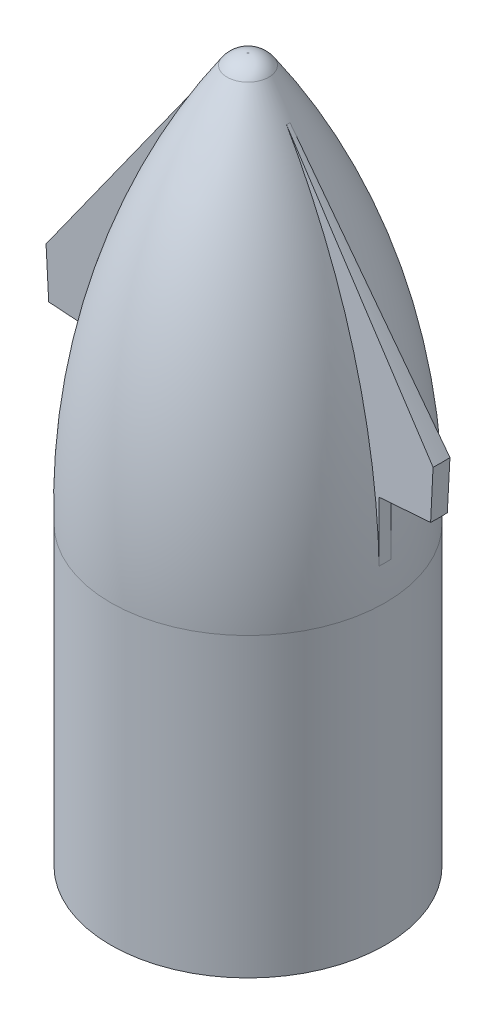
SolidWorks part; units mm, degrees
material "PET"
ref_plane "Front Plane" through (0, 0, 0) normal (0, 0, 1) x (1, 0, 0)
ref_plane "Top Plane" through (0, 0, 0) normal (0, 1, 0) x (1, 0, 0)
ref_plane "Right Plane" through (0, 0, 0) normal (1, 0, 0) x (0, 0, -1)
sketch "Sketch1" plane through (0, 0, 0) normal (0, 0, 1) x (1, 0, 0)
  line L0 (0, 0) -> (50.9, 0)
  line L1 (50.9, 0) -> (50.9, 110)
  line L2 (0, 3) -> (47.9, 3)
  line L3 (0, 261.1926) -> (0.2914, 261.1926)
  line L4 (47.9, 3) -> (47.9, 110.0403)
  line L5 (0, 258.1926) -> (0.2914, 258.1926)
  line L6 (0, 261.1926) -> (0, 258.1926)
  line L7 (0, 3) -> (0, 0)
  arc A0 (7.7342, 257.2527) -> (50.9, 110) centre (-199.0104, 116.6942) cw
  arc A1 (0.2914, 261.1926) -> (7.7342, 257.2527) centre (0.2914, 252.1926) cw
  arc A2 (5.2533, 255.566) -> (47.9, 110.0403) centre (-199.0104, 116.6942) cw
  arc A3 (0.2914, 258.1926) -> (5.2533, 255.566) centre (0.2914, 252.1926) cw
  point P10 (5, 261.1926)
  dimension "D4" = 5
  dimension "D5" = 250
  dimension "D6" = 9
  dimension "D1" = 50.9
  dimension "D2" = 110
  dimension "D3" = 3
revolve "Revolve1" add sketch "Sketch1" angle 360 about L6
sketch "Sketch2" plane through (0, 0, 0) normal (0, 0, 1) x (1, 0, 0)
  line L0 (-50.9, 122.859) -> (-50.9, 145)
  line L2 (-70.9, 147.3232) -> (-50.9, 145)
  line L4 (-71.8463, 165.5232) -> (-70.9, 147.3232)
  line L7 (0, 108.994) -> (0, 266.6667)
  line L8 (-71.8463, 165.5232) -> (-14.0824, 247.1525)
  line L9 (50.9, 122.859) -> (50.9, 145)
  line L10 (70.9, 147.3232) -> (50.9, 145)
  line L11 (71.8463, 165.5232) -> (70.9, 147.3232)
  line L12 (71.8463, 165.5232) -> (14.0824, 247.1525)
  arc A0 (-50.9, 122.859) -> (-14.0824, 247.1525) centre (199.0173, 116.4295) cw
  arc A1 (50.9, 122.859) -> (14.0824, 247.1525) centre (-199.0173, 116.4295) ccw
  dimension "D4" = 250
  dimension "D2" = 20
  dimension "D3" = 100
revolve "Revolve2" add sketch "Sketch2" angle 2.5 about L7
